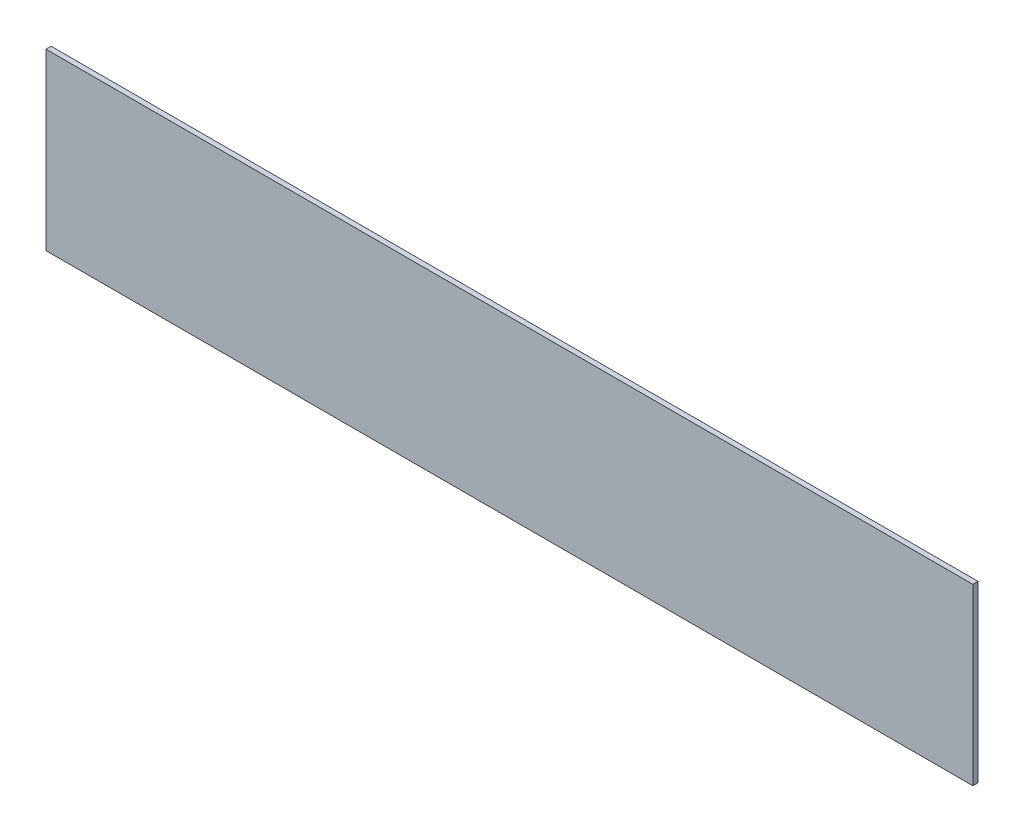
SolidWorks part; units mm, degrees
material "1060 Alloy"
ref_plane "Front" through (0, 0, 0) normal (0, 0, 1) x (1, 0, 0)
ref_plane "Top" through (0, 0, 0) normal (0, 1, 0) x (1, 0, 0)
ref_plane "Right" through (0, 0, 0) normal (1, 0, 0) x (0, 0, -1)
sketch "Sketch1" plane through (0, 0, 0) normal (0, 0, 1) x (1, 0, 0)
  line L1 (-46.6126, -26.6194) -> (182.1144, -26.6194)
  line L2 (-46.6126, -26.6194) -> (-46.6126, 16.4336)
  line L3 (-46.6126, 16.4336) -> (182.1144, 16.4336)
  line L4 (182.1144, -26.6194) -> (182.1144, 16.4336)
  dimension "D1" = 43.053
  dimension "D2" = 228.727
extrude "Boss-Extrude1" add sketch "Sketch1" along normal blind 1.27
